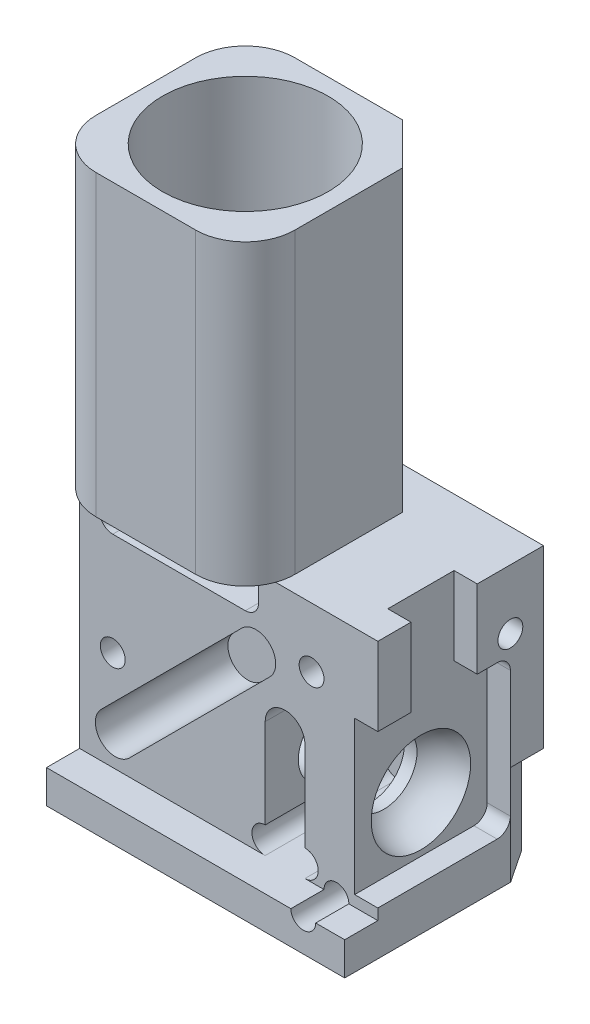
SolidWorks part; units mm, degrees
ref_plane "Front Plane" through (0, 0, 0) normal (0, 0, 1) x (1, 0, 0)
ref_plane "Top Plane" through (0, 0, 0) normal (0, 1, 0) x (1, 0, 0)
ref_plane "Right Plane" through (0, 0, 0) normal (1, 0, 0) x (0, 0, -1)
sketch "Sketch1" plane through (0, 0, 0) normal (0, 1, 0) x (1, 0, 0)
  line L1 (4.5, 3) -> (-4.5, 3)
  line L2 (4.5, 3) -> (4.5, -3)
  line L3 (4.5, -3) -> (-4.5, -3)
  line L4 (-4.5, 3) -> (-4.5, -3)
  line L5 (4.5, 3) -> (-4.5, -3) construction
  line L6 (4.5, -3) -> (-4.5, 3) construction
  point P0 (0, 0)
  dimension "D1" = 6
  dimension "D2" = 9
extrude "Main Body Ext" add sketch "Sketch1" along normal blind 8.3
sketch "Sketch8" plane through (0, 8.3, 0) normal (0, 1, 0) x (1, 0, 0)
  line L0 (0.25, 3) -> (1.5, 1.75)
  line L1 (0.25, 3) -> (-4.5, 3)
  line L2 (1.5, 1.75) -> (1.5, -3)
  line L3 (1.5, -3) -> (-4.5, -3)
  line L4 (-4.5, 3) -> (-4.5, -3)
  line L5 (0.875, 2.375) -> (-4.5, -3) construction
  line L6 (1.5, -3) -> (-4.5, 3) construction
  line L7 (-4.5, 3) -> (-4.5, -3) construction
  line L8 (0, 0) -> (-1.5, 0) construction
  point P0 (-1.5, 0)
  dimension "D1" = 6
  dimension "D2" = 6
  dimension "D3" = 1.25
  dimension "D4" = 3
extrude "Emission Path Ext" add sketch "Sketch8" along normal blind 9
sketch "Sketch3" plane through (0, 0, 0) normal (0, -1, 0) x (1, 0, 0)
  line L0 (-4.5, -3) -> (-4.5, 3) construction
  line L1 (0, 0) -> (-1.5, 0) construction
  circle A0 centre (-1.5, 0) radius 1.25
  dimension "D1" = 3
  dimension "D2" = 2.5
extrude "Emission and Grin Cut" cut sketch "Sketch3" against normal through all
sketch "Sketch4" plane through (4.5, 0, 0) normal (1, 0, 0) x (0, 0, -1)
  line L1 (-3, 0) -> (3, 0) construction
  circle A0 centre (0, 3) radius 1
  dimension "D1" = 2
  dimension "D2" = 3
extrude "Drum Lens Cut" cut sketch "Sketch4" against normal offset from surface (7 mm away) 2 up to face at (-4.5, 8.65, 0)
sketch "Sketch5" plane through (0, 0, 3) normal (0, 0, 1) x (1, 0, 0)
  line L0 (-4.5, 0) -> (4.5, 0) construction
  line L1 (4.5, 8.3) -> (-4.5, 8.3)
  line L2 (4.5, 8.3) -> (4.5, 1)
  line L3 (4.5, 1) -> (-4.5, 1)
  line L4 (-4.5, 8.3) -> (-4.5, 1)
  line L5 (4.5, 8.3) -> (-4.5, 1) construction
  line L6 (4.5, 1) -> (-4.5, 8.3) construction
  line L7 (1.5, 8.3) -> (4.5, 8.3) construction
  line L9 (4.5, 8.3) -> (4.5, 0) construction
  line L10 (-4.5, 17.3) -> (-4.5, 0) construction
  point P0 (0, 4.65)
  dimension "D1" = 1
extrude "FilterSet Cut1" cut sketch "Sketch5" against normal blind 1
sketch "Sketch6" plane through (0, 0, 2) normal (0, 0, 1) x (1, 0, 0)
  line L0 (2.3, 4.5) -> (2.3, 1.8)
  line L1 (1.1, 4.5) -> (2.3, 4.5) construction
  line L2 (2.3, 1) -> (1.1, 1)
  line L3 (-4.5, 1) -> (4.5, 1) construction
  line L4 (-4.5, 8.3) -> (-4.5, 1) construction
  line L5 (-3.9, 7.9) -> (-3.9, 7.5)
  line L6 (1.1, 4.5) -> (1.1, 1.8)
  line L7 (1.5, 8.3) -> (-4.5, 8.3) construction
  line L8 (0.9, 7.9) -> (0.9, 7.5)
  line L9 (-3, 1.5) -> (-3, 1) construction
  line L10 (0.5, 8.3) -> (-3.5, 8.3)
  line L11 (-1.5, 3) -> (-1.5, 1) construction
  line L12 (-1.5, 3) -> (0.4851, 3) construction
  line L13 (0.5, 7.1) -> (-3.5, 7.1)
  line L15 (0.5, 8.3) -> (-3.5, 7.1) construction
  line L16 (0.5, 7.1) -> (-3.5, 8.3) construction
  line L17 (1.1, 1.8) -> (2.3, 1.8) construction
  line L18 (0.3941, 6.5912) -> (-3.8485, 2.3485)
  line L19 (4.5, 1) -> (4.5, 8.3) construction
  line L20 (1.2426, 5.7426) -> (-3, 1.5)
  line L21 (0.3941, 6.5912) -> (-3, 1.5) construction
  line L22 (-3.8485, 2.3485) -> (1.2426, 5.7426) construction
  line L33 (0.5, 8.3) -> (1.102, 8.3) construction
  line L34 (1.102, 8.3) -> (1.102, 7.1) construction
  line L35 (1.102, 7.1) -> (0.5, 7.1) construction
  line L36 (-3.5, 7.1) -> (-4.098, 7.1) construction
  line L37 (-4.098, 7.1) -> (-4.098, 8.3) construction
  line L38 (-4.098, 8.3) -> (-3.5, 8.3) construction
  line L39 (-3.5, 8.3) -> (-2.7284, 6.992) construction
  arc A0 (0.5, 8.3) -> (0.9, 7.9) centre (0.5, 7.9) cw
  arc A1 (1.1, 4.5) -> (2.3, 4.5) centre (1.7, 4.5) cw
  arc A2 (-3.5, 8.3) -> (-3.9, 7.9) centre (-3.5, 7.9) ccw
  arc A3 (0.3941, 6.5912) -> (1.2426, 5.7426) centre (0.8184, 6.1669) cw
  arc A4 (1.1, 1) -> (1.1, 1.8) centre (1.1, 1.4) cw
  arc A5 (-3.8485, 2.3485) -> (-3, 1.5) centre (-3.4243, 1.9243) ccw
  arc A6 (2.3, 1) -> (2.3, 1.8) centre (2.3, 1.4) ccw
  arc A7 (-3.5, 7.1) -> (-3.9, 7.5) centre (-3.5, 7.5) cw
  arc A8 (0.5, 7.1) -> (0.9, 7.5) centre (0.5, 7.5) ccw
  point P5 (-1.5, 7.7)
  point P10 (-1.3029, 4.0456)
  dimension "D10" = 0.5
  dimension "D5" = 2.2
  dimension "D8" = 0.4
  dimension "D11" = 0.4
  dimension "D12" = 0.4
  dimension "D1" = 1.2
  dimension "D2" = 45
  dimension "D3" = 3.5
  dimension "D4" = 1.2
  dimension "D6" = 2
  dimension "D7" = 4
  dimension "D9" = 3
  dimension "D13" = 1.2
  dimension "D14" = 3
  dimension "D15" = 6
extrude "FilterSet Cut2" cut sketch "Sketch6" against normal offset from surface (4 mm away) 1 up to face at (0.4375, 9.2833, -3)
sketch "Sketch10" plane through (0, 17.3, 0) normal (0, 1, 0) x (1, 0, 0)
  line L0 (-1.5, 0) -> (-1.5, -3) construction
  line L1 (-4.5, -3) -> (1.5, -3) construction
  line L3 (-1.5, 0) -> (-4.5, 0) construction
  line L4 (-4.5, 3) -> (-4.5, -3) construction
  circle A0 centre (-1.5, 0) radius 2.5
  dimension "D1" = 5
extrude "Emission Lens Cut" cut sketch "Sketch10" against normal offset from surface (8.5 mm away) 0.5
sketch "Sketch12" plane through (4.5, 0, 0) normal (1, 0, 0) x (0, 0, -1)
  line L0 (0, 3.635) -> (0, 0) construction
  line L1 (1.6, 5.94) -> (-1.6, 5.94)
  line L2 (1.6, 5.94) -> (1.6, 1.33) construction
  line L3 (-2, 1.33) -> (1.6, 1.33)
  line L4 (-1.6, 5.94) -> (-1.6, 1.33) construction
  line L5 (1.6, 5.94) -> (-1.6, 1.33) construction
  line L6 (1.6, 1.33) -> (-1.6, 5.94) construction
  line L7 (-3, 0) -> (3, 0) construction
  line L9 (-1.6, 5.94) -> (-2, 5.94)
  line L10 (-2, 1) -> (-2, 8.3) construction
  line L11 (-2, 5.94) -> (-2, 1.33)
  line L12 (2, 5.54) -> (2, 1.73)
  arc A1 (1.6, 5.94) -> (2, 5.54) centre (1.6, 5.54) cw
  arc A2 (1.6, 1.33) -> (2, 1.73) centre (1.6, 1.73) ccw
  circle A3 centre (0, 3) radius 1 construction
  point P0 (0, 3.635)
  dimension "D2" = 4.61
  dimension "D3" = 1.67
  dimension "D1" = 3.2
  dimension "D4" = 0.4
sketch "Sketch15" plane through (0, 0, 0) normal (0, -1, 0) x (1, 0, 0)
  line L0 (-3.25, 1.875) -> (-3.25, -1.875) construction
  line L2 (1.5, 0) -> (-1.5, 0) construction
  line L3 (-1.5, 0) -> (-3.25, 0) construction
  circle A0 centre (-3.25, -1.875) radius 0.795
  circle A1 centre (-3.25, 1.875) radius 0.795
  circle A2 centre (1.5, 0) radius 0.795
  dimension "D4" = 1.59
  dimension "D1" = 3.75
  dimension "D2" = 3
  dimension "D3" = 1.75
extrude "Magnets Cut" cut sketch "Sketch15" against normal blind 0.9
sketch "Sketch18" plane through (0, 0, 2) normal (0, 0, 1) x (1, 0, 0)
  line L0 (-4.5, 8.3) -> (-4.5, 1) construction
  line L1 (4.5, 1) -> (4.5, 8.3) construction
  line L2 (4.5, 8.3) -> (1.5, 8.3) construction
  line L3 (-4.5, 0) -> (4.5, 0) construction
  line L7 (-4.5, 1) -> (1.1, 1) construction
  line L9 (-4.5, 1) -> (-4.5, 0) construction
  circle A0 centre (-3.5, 4) radius 0.375
  circle A1 centre (2.5, 6.5) radius 0.375
  circle A2 centre (3.25, 1) radius 0.375
  dimension "D1" = 0.75
  dimension "D2" = 1
  dimension "D3" = 1.8
  dimension "D4" = 2
  dimension "D5" = 3
  dimension "D6" = 1
  dimension "D7" = 7.75
extrude "Screw Holes Cut" cut sketch "Sketch18" against normal blind 3 and the other way through all
fillet "External Fillet 1" radius 1.5 2 edges at (-4.5, 8.65, -3)
sketch "Sketch14" plane through (0, 0, 0) normal (0, -1, 0) x (1, 0, 0)
  line L0 (4.5, -3) -> (4.5, -2.0067)
  line L1 (4.5, 3) -> (4.5, -3) construction
  line L2 (4.5, -2.0067) -> (3.8378, -3)
  line L3 (4.5, -3) -> (-3, -3) construction
  line L4 (3.8378, -3) -> (4.5, -3)
  line L5 (4.5, -3) -> (-4.5, 3) construction
  line L6 (-4.5, -1.5) -> (-4.5, 3) construction
  line L7 (-4.5, 3) -> (4.5, 3) construction
  dimension "D1" = 1.1938
sketch "Sketch28" plane through (0, 7.1, 0) normal (0, 1, 0) x (1, 0, 0)
  circle A0 centre (-1.5, 0) radius 1.5
  dimension "D1" = 3
extrude "Cut-Extrude8" cut sketch "Sketch28" against normal blind 4 and the other way through all
extrude "Cut-Extrude9" cut sketch "Sketch14" against normal blind 3
extrude "Cut-Extrude10" cut sketch "Sketch12" against normal blind 0.7
sketch "Sketch29" plane through (4.5, 0, 0) normal (1, 0, 0) x (0, 0, -1)
  line L0 (3, 8.3) -> (3, 3) construction
  line L1 (-2, 8.3) -> (3, 8.3) construction
  circle A0 centre (2, 6.5) radius 0.375
  dimension "D1" = 0.75
  dimension "D2" = 1
  dimension "D3" = 1.8
extrude "Cut-Extrude11" cut sketch "Sketch29" against normal blind 2.5
sketch "Sketch31" plane through (3.8, 0, 0) normal (1, 0, 0) x (0, 0, -1)
  circle A0 centre (0, 3) radius 1.6
  dimension "D1" = 3.2
sketch "Sketch32" plane through (4.5, 0, 0) normal (1, 0, 0) x (0, 0, -1)
  line L0 (-2, 8.3) -> (3, 8.3) construction
  line L1 (-1, 8.3) -> (1, 8.3)
  line L2 (-1, 8.3) -> (-1, 5.94)
  line L3 (-1, 5.94) -> (1, 5.94)
  line L4 (1, 8.3) -> (1, 5.94)
  line L5 (1.6, 5.94) -> (-2, 5.94) construction
  line L6 (-2, 5.94) -> (-2, 8.3) construction
  line L8 (3, 8.3) -> (3, 3) construction
  dimension "D1" = 1
  dimension "D2" = 2
extrude "Cut-Extrude14" cut sketch "Sketch32" against normal up to surface (0.7 mm away) up to face at (3.8, 3.635, -0.5609)
sketch "Sketch33" plane through (0, 0, 0) normal (0, 0, 1) x (1, 0, 0)
  line L0 (3.8, 3) -> (2.3, 3)
  line L1 (3.8, 1.4) -> (3.8, 4.6) construction
  line L2 (3.8, 3) -> (3.8, 4.5)
  arc A0 (2.3, 3) -> (3.8, 4.5) centre (3.8, 3) cw
  dimension "D2" = 1.5
revolve "Cut-Revolve1" cut sketch "Sketch33" angle 360 about L0
sketch "Sketch36" plane through (0, 17.3, 0) normal (0, 1, 0) x (1, 0, 0)
  line L0 (-4.5, -1.5) -> (-4.5, -3)
  line L1 (-4.5, 1.5) -> (-4.5, -3) construction
  line L2 (-4.5, -3) -> (-3, -3)
  line L3 (-4.5, -3) -> (0, -3) construction
  arc A0 (-4.5, -1.5) -> (-3, -3) centre (-3, -1.5) ccw
  dimension "D1" = 1.5
  dimension "D2" = 1.5
extrude "Cut-Extrude16" cut sketch "Sketch36" against normal up to surface (9 mm away) up to face at (-1.3971, 8.3, 1.2781)
sketch "Sketch37" plane through (0, 8.8, 0) normal (0, 1, 0) x (1, 0, 0)
  circle A0 centre (-1.5, 0) radius 2
  circle A1 centre (-1.5, 0) radius 1.5 construction
  dimension "D1" = 4
extrude "Cut-Extrude17" cut sketch "Sketch37" against normal up to next
